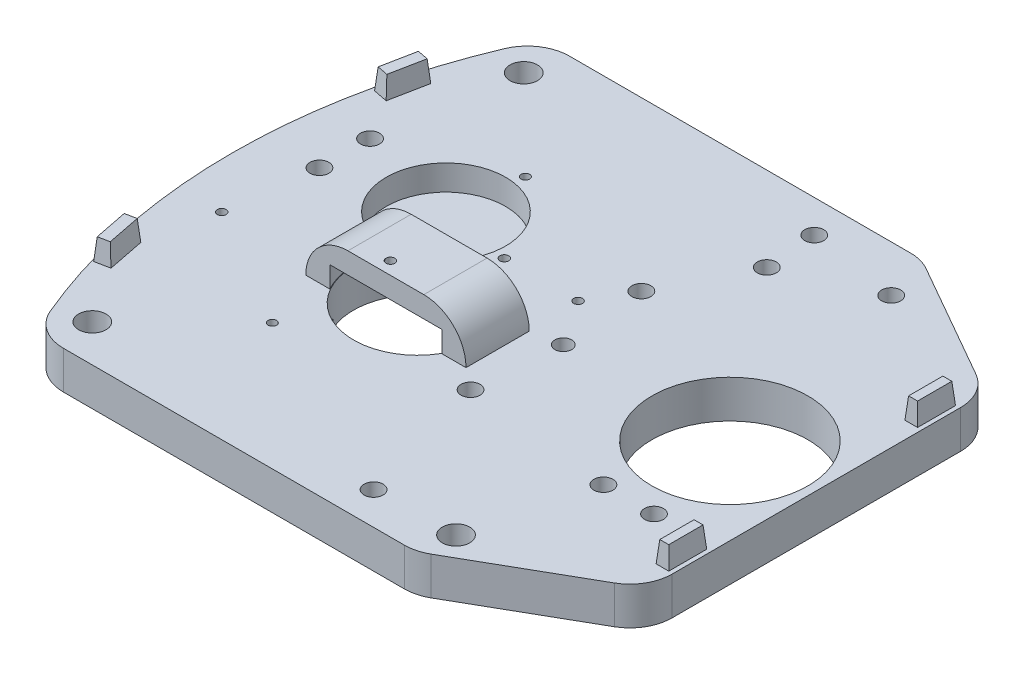
SolidWorks part; units mm, degrees
ref_plane "Front" through (0, 0, 0) normal (0, 0, 1) x (1, 0, 0)
ref_plane "Top" through (0, 0, 0) normal (0, 1, 0) x (1, 0, 0)
ref_plane "Right" through (0, 0, 0) normal (1, 0, 0) x (0, 0, -1)
sketch "Sketch1" plane through (0, 0, 0) normal (0, 1, 0) x (1, 0, 0)
  line L0 (125, 60) -> (3.8854, 60) construction
  line L1 (0, 0) -> (125, 0)
  line L2 (0, 0) -> (0, 120)
  line L3 (0, 120) -> (125, 120)
  line L4 (125, 0) -> (125, 120)
  line L5 (3.8854, 127.5) -> (3.8854, -7.5) construction
  arc A0 (3.8854, 127.5) -> (3.8854, -7.5) centre (125, 60) ccw
  dimension "D1" = 125
  dimension "D2" = 120
  dimension "D3" = 135
extrude "Top_Base" add sketch "Sketch1" along normal blind 9 contours L2 A0 | L1 L4 L3 L2 region at (62.5, 0, -60) region at (-5.4854, 0, -60)
sketch "Fingers_Position" plane through (0, 9, 0) normal (0, 1, 0) x (1, 0, 0)
  line L5 (67.75, 3.25) -> (12.75, 3.25) construction
  line L6 (67.75, 3.25) -> (67.75, 35.25) construction
  line L7 (67.75, 35.25) -> (12.75, 35.25) construction
  line L8 (12.75, 3.25) -> (12.75, 35.25) construction
  line L10 (67.75, 19.25) -> (26, 19.25) construction
  line L11 (77.75, 104.5) -> (77.75, 49.5) construction
  line L12 (35.75, 35.25) -> (35.75, 3.25) construction
  line L13 (40.75, 35.25) -> (40.75, 3.25) construction
  line L14 (125, 60) -> (-13.6542, 60) construction
  line L15 (35.75, 84.75) -> (35.75, 116.75) construction
  line L16 (26, 19.25) -> (26, 30) construction
  line L18 (77.75, 49.5) -> (109.75, 49.5) construction
  line L19 (109.75, 49.5) -> (109.75, 104.5) construction
  line L20 (109.75, 104.5) -> (77.75, 104.5) construction
  line L21 (92.5, 69) -> (92.5, 31) construction
  line L22 (92.5, 31) -> (116.5, 31) construction
  line L23 (116.5, 31) -> (116.5, 69) construction
  line L24 (116.5, 69) -> (92.5, 69) construction
  line L25 (93.75, 104.5) -> (93.75, 60) construction
  line L26 (104.5, 31) -> (104.5, 60) construction
  line L27 (26, 100.75) -> (26, 90) construction
  line L28 (40.75, 84.75) -> (40.75, 116.75) construction
  line L29 (67.75, 100.75) -> (26, 100.75) construction
  line L30 (12.75, 116.75) -> (12.75, 84.75) construction
  line L31 (67.75, 84.75) -> (12.75, 84.75) construction
  line L32 (67.75, 116.75) -> (67.75, 84.75) construction
  line L33 (67.75, 116.75) -> (12.75, 116.75) construction
  line L34 (26, 72.5) -> (26, 47.5) construction
  line L35 (92.5, 36) -> (98.5, 36) construction
  line L36 (98.5, 36) -> (98.5, 31) construction
  line L37 (116.5, 36) -> (110.5, 36) construction
  line L38 (110.5, 36) -> (110.5, 31) construction
  line L39 (93.75, 60) -> (104.5, 60) construction
  line L40 (77.75, 77.5) -> (109.75, 77.5) construction
  line L41 (125, 0) -> (125, 120) construction
  line L42 (67.75, 75.75) -> (58.75, 75.75) construction
  line L43 (67.75, 35.25) -> (58.75, 35.25) construction
  line L44 (67.75, 35.25) -> (67.75, 44.25) construction
  line L45 (67.75, 44.25) -> (58.75, 44.25) construction
  line L46 (58.75, 35.25) -> (58.75, 44.25) construction
  line L47 (58.75, 84.75) -> (58.75, 75.75) construction
  line L48 (67.75, 84.75) -> (58.75, 84.75) construction
  line L49 (67.75, 84.75) -> (67.75, 75.75) construction
  circle A1 centre (26, 30) radius 16.25 construction
  circle A3 centre (26, 30) radius 17.5 construction
  circle A5 centre (26, 30) radius 15 construction
  circle A6 centre (104.5, 60) radius 9 construction
  circle A7 centre (104.5, 60) radius 17.75 construction
  circle A8 centre (26, 30) radius 1 construction
  circle A9 centre (39.1696, 51.25) radius 7.5 construction
  circle A10 centre (39.1696, 51.25) radius 8.75 construction
  circle A11 centre (39.1696, 51.25) radius 10 construction
  circle A12 centre (39.1696, 68.75) radius 10 construction
  circle A13 centre (39.1696, 68.75) radius 8.75 construction
  circle A14 centre (39.1696, 68.75) radius 7.5 construction
  circle A15 centre (26, 90) radius 1 construction
  circle A16 centre (26, 90) radius 15 construction
  circle A17 centre (26, 90) radius 17.5 construction
  circle A18 centre (26, 90) radius 16.25 construction
  circle A19 centre (98.5, 36) radius 2.25 construction
  circle A20 centre (110.5, 36) radius 2.25 construction
  arc A21 (0, 120) -> (0, 0) centre (125, 60) ccw construction
  dimension "D3" = 32.5
  dimension "D4" = 35
  dimension "D6" = 30
  dimension "D10" = 18
  dimension "D11" = 35.5
  dimension "D19" = 2
  dimension "D20" = 20
  dimension "D21" = 17.5
  dimension "D22" = 15
  dimension "D29" = 4.5
  dimension "D5" = 32
  dimension "D7" = 55
  dimension "D8" = 24
  dimension "D9" = 38
  dimension "D14" = 10
  dimension "D2" = 27
  dimension "D15" = 55
  dimension "D16" = 32
  dimension "D17" = 41.75
  dimension "D18" = 10.75
  dimension "D23" = 25
  dimension "D13" = 29
  dimension "D25" = 6
  dimension "D26" = 6
  dimension "D27" = 5
  dimension "D28" = 5
  dimension "D12" = 44.5
  dimension "D30" = 10.75
  dimension "D31" = 27
  dimension "D24" = 8.5
  dimension "D32" = 32
  dimension "D33" = 9
  dimension "D34" = 9
sketch "Intermediate_Gear_Position" plane through (0, 9, 0) normal (0, 1, 0) x (1, 0, 0)
  line L0 (-5.25, 73.4139) -> (23.75, 73.4139) construction
  line L1 (35.75, 84.75) -> (35.75, 116.75) construction
  line L2 (32.75, 85.4139) -> (32.75, 61.4139) construction
  line L3 (-0.25, 79.4139) -> (-0.25, 85.4139) construction
  line L4 (32.75, 85.4139) -> (-5.25, 85.4139) construction
  line L6 (-5.25, 85.4139) -> (-5.25, 61.4139) construction
  line L7 (32.75, 61.4139) -> (-5.25, 61.4139) construction
  line L21 (-0.25, 67.4139) -> (-0.25, 61.4139) construction
  circle A0 centre (39.1696, 51.25) radius 14 construction
  circle A4 centre (39.1696, 51.25) radius 15 construction
  circle A6 centre (23.75, 73.4139) radius 14 construction
  circle A8 centre (39.1696, 51.25) radius 13 construction
  circle A10 centre (-0.25, 67.4139) radius 2.25 construction
  circle A11 centre (23.75, 73.4139) radius 13 construction
  circle A12 centre (-0.25, 79.4139) radius 2.25 construction
  circle A13 centre (23.75, 73.4139) radius 12 construction
  dimension "D2" = 30
  dimension "D6" = 28
  dimension "D4" = 26
  dimension "D18" = 4.5
  dimension "D22" = 4.5
  dimension "D3" = 28
  dimension "D10" = 26
  dimension "D11" = 24
  dimension "D8" = 38
  dimension "D5" = 6
  dimension "D7" = 24
  dimension "D16" = 5
  dimension "D19" = 6
  dimension "D21" = 5
  dimension "D9" = 29
  dimension "D12" = 3
sketch "Sketch5" plane through (0, 9, 0) normal (0, 1, 0) x (1, 0, 0)
  circle A1 centre (23.75, 73.4139) radius 14.15
  dimension "D1" = 28.3
extrude "Drive_Gear_Hole" cut sketch "Sketch5" against normal blind 6
sketch "Sketch8" plane through (0, 9, 0) normal (0, 1, 0) x (1, 0, 0)
  circle A1 centre (104.5, 60) radius 18.5
  dimension "D2" = 37
sketch "Sketch28" plane through (0, 9, 0) normal (0, 1, 0) x (1, 0, 0)
  circle A0 centre (39.1696, 51.25) radius 15.15
  dimension "D1" = 30.3
extrude "Two_Stage_Gear_Hole" cut sketch "Sketch28" against normal through all
extrude "XL320_Finger_Knuckle_Mount" cut sketch "Sketch8" against normal through all
sketch "XL320_Mount_Holes" plane through (0, 9, 0) normal (0, 1, 0) x (1, 0, 0)
  line L0 (116.5, 36) -> (110.5, 36) construction
  circle A13 centre (110.5, 36) radius 2.25
  circle A15 centre (98.5, 36) radius 2.25
  circle A16 centre (-0.25, 79.4139) radius 2.25
  circle A17 centre (-0.25, 67.4139) radius 2.25
  dimension "D5" = 4.5
sketch "AX12_Mount_Holes" plane through (0, 9, 0) normal (0, 1, 0) x (1, 0, 0)
  line L0 (67.75, 116.75) -> (72.25, 116.75) construction
  line L1 (67.75, 116.75) -> (12.75, 116.75) construction
  line L2 (72.25, 116.75) -> (72.25, 112.25) construction
  line L3 (67.75, 84.75) -> (67.75, 80.25) construction
  line L4 (67.75, 80.25) -> (63.25, 80.25) construction
  line L5 (93.75, 104.5) -> (93.75, 109) construction
  line L7 (109.75, 104.5) -> (77.75, 104.5) construction
  line L8 (77.75, 104.5) -> (73.25, 104.5) construction
  line L9 (73.25, 104.5) -> (73.25, 100) construction
  line L10 (67.75, 35.25) -> (67.75, 39.75) construction
  line L11 (67.75, 39.75) -> (63.25, 39.75) construction
  line L12 (67.75, 3.25) -> (72.25, 3.25) construction
  line L13 (67.75, 3.25) -> (12.75, 3.25) construction
  line L14 (72.25, 3.25) -> (72.25, 7.75) construction
  circle A4 centre (72.25, 112.25) radius 2.25
  circle A5 centre (63.25, 80.25) radius 2.25
  circle A6 centre (73.25, 100) radius 2.25
  circle A7 centre (93.75, 109) radius 2.25
  circle A8 centre (63.25, 39.75) radius 2.25
  circle A9 centre (72.25, 7.75) radius 2.25
  dimension "D2" = 4.5
  dimension "D1" = 4.5
sketch "Sketch26" plane through (0, 9, 0) normal (0, -1, 0) x (1, 0, 0)
  line L0 (26, -12.5) -> (26, -30) construction
  line L2 (-13.6542, -60) -> (125, -60) construction
  circle A0 centre (26, -30) radius 17.5 construction
  circle A1 centre (26, -30) radius 1
  circle A2 centre (26, -90) radius 1
  dimension "D2" = 2
extrude "String_Holes" cut sketch "Sketch26" along normal through all
extrude "XL320_Mount_Holes_(M4)" cut sketch "XL320_Mount_Holes" against normal through all
extrude "AX12_Mount_Holes_(M4)" cut sketch "AX12_Mount_Holes" against normal through all
sketch "Sketch27" plane through (0, 0, 0) normal (0, -1, 0) x (1, 0, 0)
  line L0 (110.5, -31.9585) -> (107, -33.9793)
  line L2 (107, -33.9793) -> (107, -38.0207)
  line L3 (107, -38.0207) -> (110.5, -40.0415)
  line L5 (110.5, -40.0415) -> (114, -38.0207)
  line L6 (114, -38.0207) -> (114, -33.9793)
  line L8 (114, -33.9793) -> (110.5, -31.9585)
  line L13 (110.5, -31.9585) -> (110.5, -40.0415) construction
  line L14 (107, -33.9793) -> (114, -38.0207) construction
  line L16 (114, -33.9793) -> (107, -38.0207) construction
  line L17 (98.5, -31.9585) -> (95, -33.9793)
  line L18 (95, -33.9793) -> (102, -38.0207) construction
  line L19 (95, -33.9793) -> (95, -38.0207)
  line L20 (102, -33.9793) -> (95, -38.0207) construction
  line L21 (98.5, -31.9585) -> (98.5, -40.0415) construction
  line L22 (102, -38.0207) -> (102, -33.9793)
  line L23 (95, -38.0207) -> (98.5, -40.0415)
  line L24 (98.5, -40.0415) -> (102, -38.0207)
  line L25 (102, -33.9793) -> (98.5, -31.9585)
  line L26 (3.25, -65.3931) -> (-0.25, -63.3724)
  line L27 (3.25, -69.4346) -> (3.25, -65.3931)
  line L28 (-3.75, -65.3931) -> (-3.75, -69.4346)
  line L29 (-0.25, -63.3724) -> (-0.25, -71.4553) construction
  line L30 (-3.75, -65.3931) -> (3.25, -69.4346) construction
  line L31 (-0.25, -63.3724) -> (-3.75, -65.3931)
  line L32 (-0.25, -71.4553) -> (3.25, -69.4346)
  line L33 (-3.75, -69.4346) -> (-0.25, -71.4553)
  line L34 (3.25, -65.3931) -> (-3.75, -69.4346) construction
  line L35 (-3.75, -77.3931) -> (3.25, -81.4346) construction
  line L36 (-3.75, -77.3931) -> (-3.75, -81.4346)
  line L37 (-0.25, -83.4553) -> (3.25, -81.4346)
  line L38 (-0.25, -75.3724) -> (-3.75, -77.3931)
  line L39 (3.25, -81.4346) -> (3.25, -77.3931)
  line L40 (-0.25, -75.3724) -> (-0.25, -83.4553) construction
  line L41 (3.25, -77.3931) -> (-0.25, -75.3724)
  line L42 (3.25, -77.3931) -> (-3.75, -81.4346) construction
  line L43 (-3.75, -81.4346) -> (-0.25, -83.4553)
  circle A4 centre (110.5, -36) radius 3.5 construction
  circle A5 centre (98.5, -36) radius 3.5 construction
  circle A6 centre (98.5, -36) radius 2.25 construction
  circle A7 centre (-0.25, -67.4139) radius 3.5 construction
  circle A8 centre (-0.25, -67.4139) radius 2.25 construction
  circle A9 centre (-0.25, -79.4139) radius 3.5 construction
  circle A21 centre (-0.25, -79.4139) radius 2.25 construction
  dimension "D1" = 7
  dimension "D3" = 7
  dimension "D5" = 7
  dimension "D7" = 7
  dimension "D2" = 60
  dimension "D4" = 60
  dimension "D6" = 60
  dimension "D8" = 60
extrude "Nuts_(M4)" cut sketch "Sketch27" against normal blind 5
sketch "Sketch34" plane through (0, 0, 0) normal (0, -1, 0) x (1, 0, 0)
  circle A0 centre (26, -30) radius 15
  circle A1 centre (26, -90) radius 15
  circle A2 centre (26, -90) radius 11.75 construction
  dimension "D1" = 30
  dimension "D2" = 23.5
extrude "Holes_For_M4_In_Finger_Gear" cut sketch "Sketch34" against normal blind 2
sketch "Sketch31" plane through (0, 9, 0) normal (0, 1, 0) x (1, 0, 0)
  line L1 (58.1696, 43.75) -> (20.1696, 43.75)
  line L2 (58.1696, 43.75) -> (58.1696, 58.75)
  line L3 (58.1696, 58.75) -> (20.1696, 58.75)
  line L4 (20.1696, 43.75) -> (20.1696, 58.75)
  line L5 (58.1696, 43.75) -> (20.1696, 58.75) construction
  line L6 (58.1696, 58.75) -> (20.1696, 43.75) construction
  point P0 (39.1696, 51.25)
  dimension "D1" = 38
  dimension "D2" = 15
extrude "Boss-Extrude1" add sketch "Sketch31" along normal blind 10
sketch "Sketch32" plane through (0, 9, 0) normal (0, -1, 0) x (1, 0, 0)
  circle A0 centre (39.1696, -51.25) radius 15.25
  dimension "D1" = 30.5
extrude "Cut-Extrude5" cut sketch "Sketch32" against normal blind 5
sketch "Sketch33" plane through (0, 14, 0) normal (0, -1, 0) x (1, 0, 0)
  circle A0 centre (39.1696, -51.25) radius 1
  dimension "D1" = 2
extrude "Cut-Extrude6" cut sketch "Sketch33" against normal blind 2.5
fillet "Fillet2" radius 10 2 edges at (58.1696, 19, -51.25) (20.1696, 19, -51.25)
sketch "Sketch36" plane through (0, 9, 0) normal (0, 1, 0) x (1, 0, 0)
  line L0 (90, 120) -> (125, 100)
  line L1 (0, 120) -> (125, 120) construction
  line L2 (125, 0) -> (125, 120) construction
  line L3 (125, 100) -> (125, 120)
  line L4 (125, 120) -> (90, 120)
  line L5 (-13.6542, 60) -> (125, 60) construction
  line L6 (125, 0) -> (90, 0)
  line L7 (125, 20) -> (125, 0)
  line L8 (90, 0) -> (125, 20)
  dimension "D1" = 35
  dimension "D4" = 20
extrude "Cut-Extrude8" cut sketch "Sketch36" against normal through all
fillet "Fillet4" radius 10 6 edges at (0, 4.5, 0) (90, 4.5, 0) (125, 4.5, -20) (125, 4.5, -100) (90, 4.5, -120) (0, 4.5, -120)
sketch "Sketch37" plane through (0, 9, 0) normal (0, 1, 0) x (1, 0, 0)
  line L0 (6.4592, 120) -> (6.4592, 0) construction
  line L1 (87.3444, 120) -> (87.3444, 0) construction
  line L2 (6.4592, 111.1529) -> (4.4592, 111.1529) construction
  line L3 (4.4592, 111.1529) -> (0.9304, 118.3326) construction
  line L4 (-13.6542, 60) -> (125, 60) construction
  line L5 (4.4592, 8.8471) -> (0.9304, 1.6674) construction
  line L6 (6.4592, 8.8471) -> (4.4592, 8.8471) construction
  line L7 (91.3444, 8.2056) -> (87.3444, 8.2056) construction
  line L10 (91.3444, 8.2056) -> (89.911, 0.335) construction
  arc A0 (87.3444, 0) -> (92.3057, 1.3176) centre (87.3444, 10) ccw construction
  circle A1 centre (4.4592, 111.1529) radius 3.25
  arc A2 (6.4592, 120) -> (-2.7547, 113.8864) centre (6.4592, 110) ccw construction
  circle A3 centre (4.4592, 8.8471) radius 3.25
  circle A4 centre (91.3444, 8.2056) radius 3.25
  dimension "D1" = 6.5
  dimension "D4" = 6.5
  dimension "D2" = 8
  dimension "D3" = 2
  dimension "D5" = 4
  dimension "D6" = 8
extrude "Connect_Holes_(M6)" cut sketch "Sketch37" against normal blind 10
sketch "Sketch41" plane through (0, 9, 0) normal (0, 1, 0) x (1, 0, 0)
  line L0 (125, 60) -> (-13.6542, 60) construction
  line L1 (125, 60) -> (65, 60) construction
  line L2 (125, 25.8032) -> (125, 94.1968) construction
  circle A0 centre (65, 60) radius 2
  dimension "D2" = 4
  dimension "D1" = 60
extrude "Connect_To_House_(M4)" cut sketch "Sketch41" against normal through all
sketch "Sketch42" plane through (0, 9, 0) normal (0, 1, 0) x (1, 0, 0)
  line L5 (-13.6542, 60) -> (125, 60) construction
  line L6 (124, 26) -> (121, 26)
  line L7 (124, 26) -> (124, 35)
  line L8 (124, 35) -> (121, 35)
  line L9 (121, 26) -> (121, 35)
  line L10 (-13.6542, 60) -> (-3.3496, 8.0542) construction
  line L11 (-9.5334, 30.2329) -> (-6.1003, 30.9139)
  line L12 (-6.1003, 30.9139) -> (-4.349, 22.0859)
  line L13 (-4.349, 22.0859) -> (-7.7822, 21.4049)
  line L14 (-7.7822, 21.4049) -> (-9.5334, 30.2329)
  line L15 (125, 25.8032) -> (125, 94.1968) construction
  line L16 (-4.349, 97.9141) -> (-7.7822, 98.5951)
  line L17 (-6.1003, 89.0861) -> (-4.349, 97.9141)
  line L18 (-7.7822, 98.5951) -> (-9.5334, 89.7671)
  line L19 (-9.5334, 89.7671) -> (-6.1003, 89.0861)
  line L20 (124, 94) -> (121, 94)
  line L21 (121, 94) -> (121, 85)
  line L22 (124, 85) -> (121, 85)
  line L23 (124, 94) -> (124, 85)
  arc A1 (-2.7547, 6.1136) -> (6.4592, 0) centre (6.4592, 10) ccw construction
  point P16 (-7.8168, 30.5734)
  dimension "D1" = 3
  dimension "D2" = 9
  dimension "D3" = 25
  dimension "D4" = 9
  dimension "D5" = 3.5
  dimension "D6" = 30
  dimension "D7" = 1
extrude "Housing_Fits" add sketch "Sketch42" along normal blind 5 draft 5
sketch "Sketch43" plane through (0, 0, 0) normal (0, -1, 0) x (1, 0, 0)
  circle A0 centre (39.1696, -68.75) radius 1
  dimension "D1" = 2
extrude "M2_Shaft_Hole" cut sketch "Sketch43" against normal blind 2
sketch "Sketch39" plane through (0, 9, 0) normal (0, 1, 0) x (1, 0, 0)
  line L0 (37.25, 46.75) -> (-2.75, 46.75) construction
  line L5 (37.25, 46.75) -> (40.25, 46.75) construction
  line L6 (67.75, 75.75) -> (58.75, 75.75) construction
  line L7 (77.75, 104.5) -> (77.75, 49.5) construction
  line L9 (40.25, 70.75) -> (37.25, 46.75) construction
  line L11 (40.25, 46.75) -> (40.25, 70.75) construction
  line L12 (40.25, 70.75) -> (57.75, 70.75) construction
  line L16 (56.75, 70.75) -> (39.25, 70.75) construction
  circle A0 centre (40.25, 70.75) radius 2.5 construction
  circle A1 centre (-2.75, 46.75) radius 2.5 construction
  circle A2 centre (37.25, 46.75) radius 2.5 construction
  circle A3 centre (57.75, 70.75) radius 2.5 construction
  circle A4 centre (-2.75, 46.75) radius 1 construction
  circle A5 centre (37.25, 46.75) radius 1 construction
  circle A6 centre (40.25, 70.75) radius 1 construction
  circle A7 centre (57.75, 70.75) radius 1 construction
  dimension "D4" = 5
  dimension "D5" = 24
  dimension "D8" = 20
  dimension "D6" = 2
  dimension "D1" = 40
  dimension "D2" = 3
  dimension "D3" = 5
  dimension "D7" = 17.5
sketch "Sketch44" plane through (0, 9, 0) normal (0, 1, 0) x (1, 0, 0)
  circle A0 centre (-2.75, 46.75) radius 1.05
  circle A1 centre (40.25, 70.75) radius 1.05
  circle A2 centre (57.75, 70.75) radius 1.05
  dimension "D1" = 2.1
extrude "Cut-Extrude9" cut sketch "Sketch44" against normal blind 5
sketch "Sketch45" plane through (0, 19, 0) normal (0, 1, 0) x (1, 0, 0)
  circle A0 centre (37.25, 46.75) radius 1.05
  dimension "D1" = 2.1
extrude "Cut-Extrude10" cut sketch "Sketch45" against normal blind 2.5
equation "\"od1\"= 35'outside diameter finger"
equation "\"n1\"= 26'number of teeth finger"
equation "\"m1\"= \"od1\" / ( \"n1\" + 2 )'module finger"
equation "\"p1\"= \"m1\" * pi'pitch finger"
equation "\"d1\"= \"m1\" * \"n1\"'primitive diameter finger"
equation "\"da1\"= \"d1\" + 2 * \"m1\"'head diamater finger"
equation "\"df1\"= \"d1\" - 2 * \"m1\"'foot diameter finger"
equation "\"od2\"= 20'outside diameter intermediate"
equation "\"n2\"= 14'number of teeth intermediate"
equation "\"m2\"= \"od2\" / ( \"n2\" + 2 )'module intermediate"
equation "\"p2\"= \"m2\" * pi'pitch intermediate"
equation "\"d2\"= \"m2\" * \"n2\"'primitive diameter intermediate"
equation "\"da2\"= \"d2\" + 2 * \"m2\"'head diamater intermediate"
equation "\"df2\"= \"d2\" - 2 * \"m2\"'foot diameter intermediate"
equation "\"od3\"= 30'outside diameter top"
equation "\"n3\"= 28'number of teeth top"
equation "\"m3\"= \"od3\" / ( \"n3\" + 2 )'module top"
equation "\"p3\"= \"m3\" * pi'pitch top"
equation "\"d3\"= \"m3\" * \"n3\"'primitive diameter top"
equation "\"da3\"= \"d3\" + 2 * \"m3\"'head diamater top"
equation "\"df3\"= \"d3\" - 2 * \"m3\"'foot diameter top"
equation "\"od4\"= 28'outside diameter drive"
equation "\"n4\"= 26'number of teeth drive"
equation "\"m4\"= \"od4\" / ( \"n4\" + 2 )'module drive"
equation "\"p4\"= \"m4\" * pi'pitch drive"
equation "\"d4\"= \"m4\" * \"n4\"'primitive diameter drive"
equation "\"da4\"= \"d4\" + 2 * \"m4\"'head diamater drive"
equation "\"df4\"= \"d4\" - 2 * \"m4\"'foot diameter drive"
equation "\"D4@Fingers_Position\"=\"da1\""
equation "\"D3@Fingers_Position\"=\"d1\""
equation "\"D6@Fingers_Position\"=\"df1\""
equation "\"D20@Fingers_Position\"=\"da2\""
equation "\"D21@Fingers_Position\"=\"d2\""
equation "\"D22@Fingers_Position\"=\"df2\""
equation "\"D3@Intermediate_Gear_Position\"=\"d3\""
equation "\"D2@Intermediate_Gear_Position\"=\"da3\""
equation "\"D4@Intermediate_Gear_Position\"=\"df3\""
equation "\"D6@Intermediate_Gear_Position\"=\"da4\""
equation "\"D10@Intermediate_Gear_Position\"=\"d4\""
equation "\"D11@Intermediate_Gear_Position\"=\"df4\""
equation "\"D1@Sketch34\"=\"df1\""
